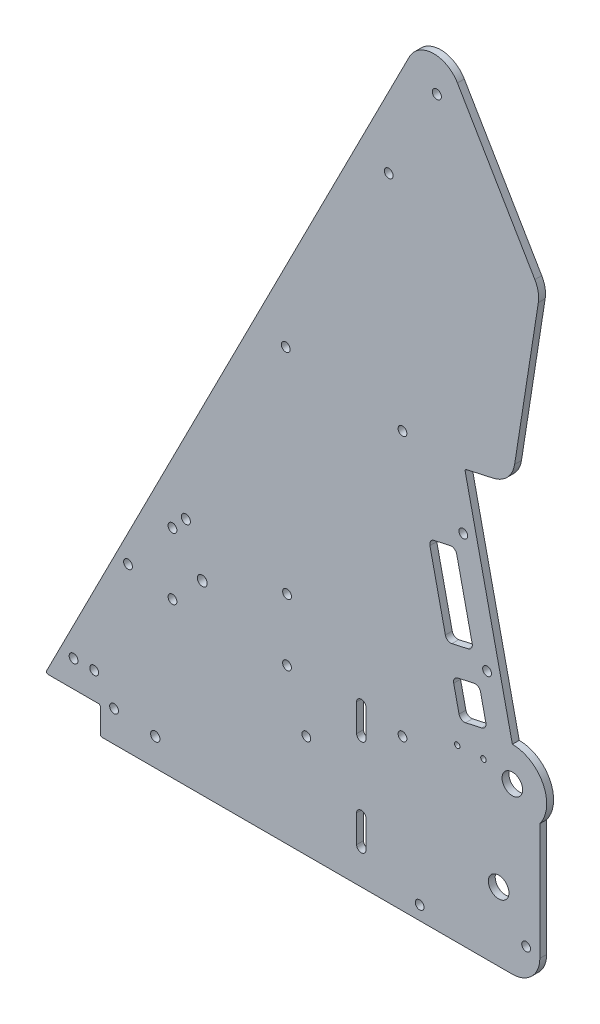
SolidWorks part; units mm, degrees
other "Markup1"
sketch "Sketch5"
ref_plane "Front Plane" through (0, 0, 0) normal (0, 0, 1) x (1, 0, 0)
ref_plane "Top Plane" through (0, 0, 0) normal (0, 1, 0) x (1, 0, 0)
ref_plane "Right Plane" through (0, 0, 0) normal (1, 0, 0) x (0, 0, -1)
sketch "Sketch1" plane through (0, 0, 0) normal (0, 0, 1) x (1, 0, 0)
  line L1 (228.6, -12.7) -> (228.6, 53.975)
  line L2 (178.7547, 351.4131) -> (0, 0)
  line L3 (228.6, 266.7) -> (178.7547, 351.4131)
  line L5 (0, 0) -> (25.4, 0)
  line L6 (25.4, 0) -> (25.4, -12.7)
  line L7 (25.4, -12.7) -> (228.6, -12.7)
  line L9 (215.9, 79.375) -> (193.9097, 178.5667)
  line L10 (193.9097, 178.5667) -> (215.6079, 183.377)
  line L11 (215.6079, 183.377) -> (228.6, 266.7)
  arc A0 (228.6, 53.975) -> (215.9, 79.375) centre (215.9, 63.5) ccw
  dimension "D7" = 12.7
  dimension "D8" = 76.2
  dimension "D10" = 31.75
  dimension "D2" = 279.4
  dimension "D3" = 25.4
  dimension "D4" = 215.9
  dimension "D5" = 394.2644
  dimension "D6" = 203.2
  dimension "D9" = 63.039
  dimension "D11" = 101.6
  dimension "D12" = 12.5
  dimension "D13" = 22.225
extrude "Boss-Extrude1" add sketch "Sketch1" along normal blind 3.175
sketch "Sketch2" plane through (0, 0, 3.175) normal (0, 0, 1) x (1, 0, 0)
  line L0 (178.7547, 351.4131) -> (0, 0) construction
  line L1 (25.4, -12.7) -> (228.6, -12.7) construction
  line L2 (215.9, 79.375) -> (193.9097, 178.5667) construction
  line L3 (193.9097, 178.5667) -> (215.6079, 183.377) construction
  line L4 (215.9, 79.375) -> (193.9097, 178.5667) construction
  line L5 (64.9432, 94.0578) -> (72.5445, 73.1732) construction
  line L6 (64.9432, 94.0578) -> (103.3734, 94.0578) construction
  line L10 (228.6, -12.7) -> (228.6, 53.975) construction
  circle A0 centre (64.9432, 94.0578) radius 2.0955
  circle A1 centre (180.975, 322.1643) radius 2.0955
  circle A2 centre (72.5445, 73.1732) radius 2.286
  circle A3 centre (193.2078, 152.3944) radius 2.032
  circle A4 centre (215.9, 63.5) radius 4.7625
  circle A7 centre (173.0375, -6.35) radius 2.032
  circle A8 centre (204.203, 102.7985) radius 2.032
  circle A26 centre (209.55, 19.05) radius 4.7625
  arc A30 (228.6, 53.975) -> (215.9, 79.375) centre (215.9, 63.5) ccw construction
  circle A31 centre (165.1, 179.3875) radius 2.032
  circle A35 centre (111.724, 87.4607) radius 2.032
  circle A36 centre (111.724, 58.8857) radius 2.032
  circle A37 centre (58.765, 58.8857) radius 2.032
  circle A38 centre (58.765, 87.4607) radius 2.032
  circle A39 centre (111.724, 58.8857) radius 1.905 construction
  circle A42 centre (111.724, 87.4607) radius 1.905 construction
  circle A43 centre (58.765, 58.8857) radius 1.905 construction
  circle A44 centre (58.765, 87.4607) radius 1.905 construction
  dimension "D3" = 4.191
  dimension "D5" = 4.191
  dimension "D9" = 4.572
  dimension "D20" = 9.525
  dimension "D23" = 9.525
  dimension "D18" = 4.064
  dimension "D26" = 4.064
  dimension "D14" = 4.064
  dimension "D10" = 4.064
  dimension "D2" = 15.24
  dimension "D6" = 15.24
  dimension "D7" = 22.225
  dimension "D21" = 44.45
  dimension "D22" = 6.35
  dimension "D19" = 160.3375
  dimension "D24" = 44.45
  dimension "D25" = 6.35
  dimension "D27" = 25.4
  dimension "D28" = 50.8
  dimension "D29" = 6.35
  dimension "D17" = 6.35
  dimension "D33" = 55.5625
  dimension "D15" = 114.3
  dimension "D4" = 180.975
  dimension "D8" = 70
extrude "Cut-Extrude1" cut sketch "Sketch2" against normal through all
sketch "Sketch7" plane through (0, 0, 3.175) normal (0, 0, 1) x (1, 0, 0)
  line L0 (146.05, 3.175) -> (146.05, 15.875) construction
  line L1 (143.891, 3.175) -> (143.891, 15.875)
  line L2 (148.209, 3.175) -> (148.209, 15.875)
  line L3 (146.05, 47.625) -> (146.05, 60.325) construction
  line L4 (143.891, 47.625) -> (143.891, 60.325)
  line L5 (148.209, 47.625) -> (148.209, 60.325)
  line L6 (25.4, -12.7) -> (228.6, -12.7) construction
  line L12 (228.6, -12.7) -> (228.6, 53.975) construction
  line L13 (25.4, -12.7) -> (228.6, -12.7) construction
  arc A0 (143.891, 3.175) -> (148.209, 3.175) centre (146.05, 3.175) ccw
  arc A1 (148.209, 15.875) -> (143.891, 15.875) centre (146.05, 15.875) ccw
  arc A2 (143.891, 47.625) -> (148.209, 47.625) centre (146.05, 47.625) ccw
  arc A3 (148.209, 60.325) -> (143.891, 60.325) centre (146.05, 60.325) ccw
  circle A8 centre (50.8, 0) radius 2.159
  point P2 (146.05, 9.525)
  point P9 (146.05, 53.975)
  dimension "D1" = 4.318
  dimension "D5" = 4.318
  dimension "D2" = 12.7
  dimension "D3" = 12.7
  dimension "D4" = 44.45
  dimension "D6" = 95.25
  dimension "D7" = 82.55
  dimension "D8" = 15.875
  dimension "D9" = 12.7
extrude "Cut-Extrude2" cut sketch "Sketch7" against normal through all
sketch "Sketch10" plane through (0, 0, 3.175) normal (0, 0, 1) x (1, 0, 0)
  circle A0 centre (120.65, 34.925) radius 2.032
  circle A1 centre (165.1, 57.15) radius 2.032
  circle A2 centre (13.0465, 12.3347) radius 2.032
  circle A3 centre (22.5715, 12.3347) radius 2.032
  circle A4 centre (38.2114, 62.6398) radius 2.032
  dimension "D1" = 4.064
  dimension "D3" = 34.925
  dimension "D2" = 120.65
  dimension "D4" = 63.5
  dimension "D5" = 69.85
extrude "Cut-Extrude3" cut sketch "Sketch10" against normal up to next
fillet "Fillet1" radius 12.7 4 edges at (228.6, -12.7, 1.5875) (178.7547, 351.4131, 1.5875) (215.6079, 183.377, 1.5875) (228.6, 266.7, 1.5875)
fillet "Fillet2" radius 0.7937 4 edges at (25.4, -12.7, 1.5875) (25.4, 0, 1.5875) (193.9097, 178.5667, 1.5875) (0, 0, 1.5875)
sketch "Sketch12" plane through (0, 0, 3.175) normal (0, 0, 1) x (1, 0, 0)
  circle A0 centre (31.75, 1.5875) radius 2.032
  circle A1 centre (173.0375, -6.35) radius 2.032
  circle A2 centre (222.25, 1.5875) radius 2.032
  dimension "D1" = 4.064
extrude "Cut-Extrude5" cut sketch "Sketch12" against normal through all
sketch "Sketch13" plane through (0, 0, 3.175) normal (0, 0, 1) x (1, 0, 0)
  line L1 (228.6, 0) -> (228.6, 53.975) construction
  line L2 (1.2943, 0) -> (24.6062, 0) construction
  line L3 (26.1937, -12.7) -> (215.9, -12.7) construction
  circle A0 centre (111.125, 186.055) radius 2.032
  circle A1 centre (158.75, 279.4) radius 2.032
  dimension "D2" = 4.064
  dimension "D5" = 4.064
  dimension "D1" = 198.755
  dimension "D3" = 69.85
  dimension "D4" = 279.4
  dimension "D6" = 117.475
extrude "Cut-Extrude6" cut sketch "Sketch13" against normal through all
sketch "Sketch14" plane through (0, 0, 3.175) normal (0, 0, 1) x (1, 0, 0)
  line L0 (177.2237, 142.3466) -> (189.6226, 145.0954)
  line L1 (189.6226, 145.0954) -> (197.869, 107.8985)
  line L2 (197.869, 107.8985) -> (185.47, 105.1497)
  line L3 (185.47, 105.1497) -> (177.2237, 142.3466)
  line L4 (187.1428, 144.5456) -> (179.7035, 142.8963) construction
  line L5 (188.2188, 92.7508) -> (200.6178, 95.4995)
  line L6 (188.2188, 92.7508) -> (191.7922, 76.6321)
  line L7 (191.7922, 76.6321) -> (204.1912, 79.3809)
  line L8 (200.6178, 95.4995) -> (204.1912, 79.3809)
  line L11 (197.3192, 110.3783) -> (190.1724, 142.6156) construction
  line L12 (177.7734, 139.8668) -> (184.9203, 107.6295) construction
  line L13 (187.9498, 105.6995) -> (195.3892, 107.3487) construction
  line L14 (203.6414, 81.8607) -> (201.1675, 93.0197) construction
  line L15 (194.272, 77.1819) -> (201.7114, 78.8311) construction
  line L16 (188.7686, 90.271) -> (191.2425, 79.1119) construction
  line L17 (198.138, 94.9498) -> (190.6986, 93.3005) construction
  circle A0 centre (190.4268, 66.2609) radius 1.27
  circle A1 centre (202.5335, 66.7895) radius 1.27
  circle A2 centre (190.4268, 66.2609) radius 1.27 construction
  circle A3 centre (202.5335, 66.7895) radius 1.27 construction
  point P8 (152.4, 88.9)
extrude "Cut-Extrude7" cut sketch "Sketch14" against normal through all both and the other way through all
fillet "Fillet3" radius 2.54 8 edges at (200.6178, 95.4995, 1.5875) (188.2188, 92.7508, 1.5875) (191.7922, 76.6321, 1.5875) (204.1912, 79.3809, 1.5875) (197.869, 107.8985, 1.5875) (185.47, 105.1497, 1.5875) (177.2237, 142.3466, 1.5875) (189.6226, 145.0954, 1.5875)
equation "\"D6@Sketch2\"=\"D2@Sketch2\""
